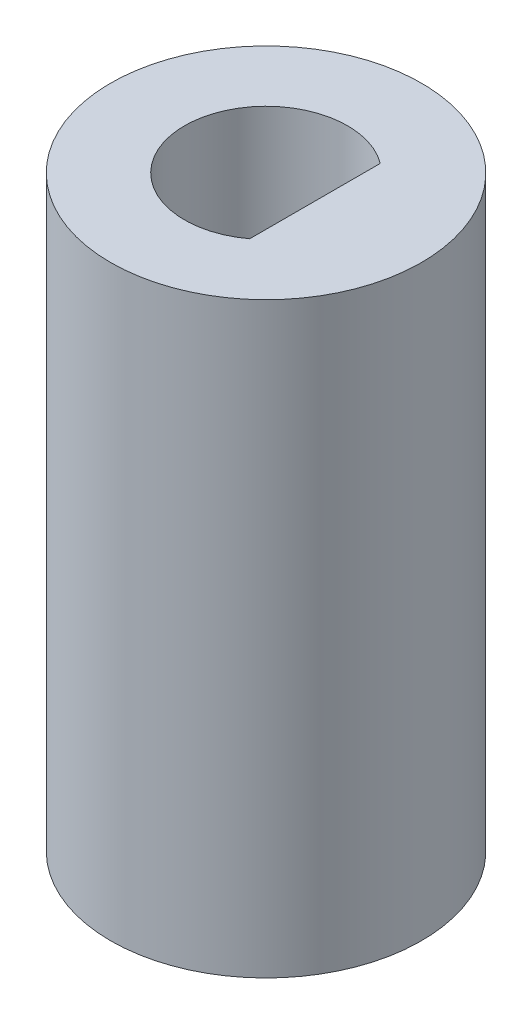
SolidWorks part; units mm, degrees
ref_plane "Front Plane" through (0, 0, 0) normal (0, 0, 1) x (1, 0, 0)
ref_plane "Top Plane" through (0, 0, 0) normal (0, 1, 0) x (1, 0, 0)
ref_plane "Right Plane" through (0, 0, 0) normal (1, 0, 0) x (0, 0, -1)
sketch "Sketch1" plane through (0, 0, 0) normal (0, 1, 0) x (1, 0, 0)
  circle A0 centre (-4.6722, 0.923) radius 4.7625
  dimension "D1" = 9.525
extrude "Boss-Extrude1" add sketch "Sketch1" along normal blind 9 and the other way blind 9
sketch "Sketch6" plane through (0, 9, 0) normal (0, 1, 0) x (1, 0, 0)
  line L0 (-3.1722, -1.077) -> (-3.1722, 2.923)
  arc A0 (-3.1722, 2.923) -> (-3.1722, -1.077) centre (-4.6722, 0.923) ccw
  arc A1 (-3.1722, -1.077) -> (-3.1722, 2.923) centre (-4.6722, 0.923) ccw construction
  point P0 (-4.6722, 0.923)
  dimension "D1" = 5
  dimension "D2" = 1.5
extrude "Cut-Extrude1" cut sketch "Sketch6" against normal blind 7
sketch "Sketch7" plane through (0, -9, 0) normal (0, -1, 0) x (1, 0, 0)
  circle A0 centre (-4.6722, -0.923) radius 4.7625 construction
  circle A1 centre (-4.6722, -0.923) radius 1.5875
  point P0 (-9.3254, -1.9375)
  point P1 (-4.6722, -0.923)
  dimension "D1" = 3.175
extrude "Cut-Extrude2" cut sketch "Sketch7" against normal blind 7
